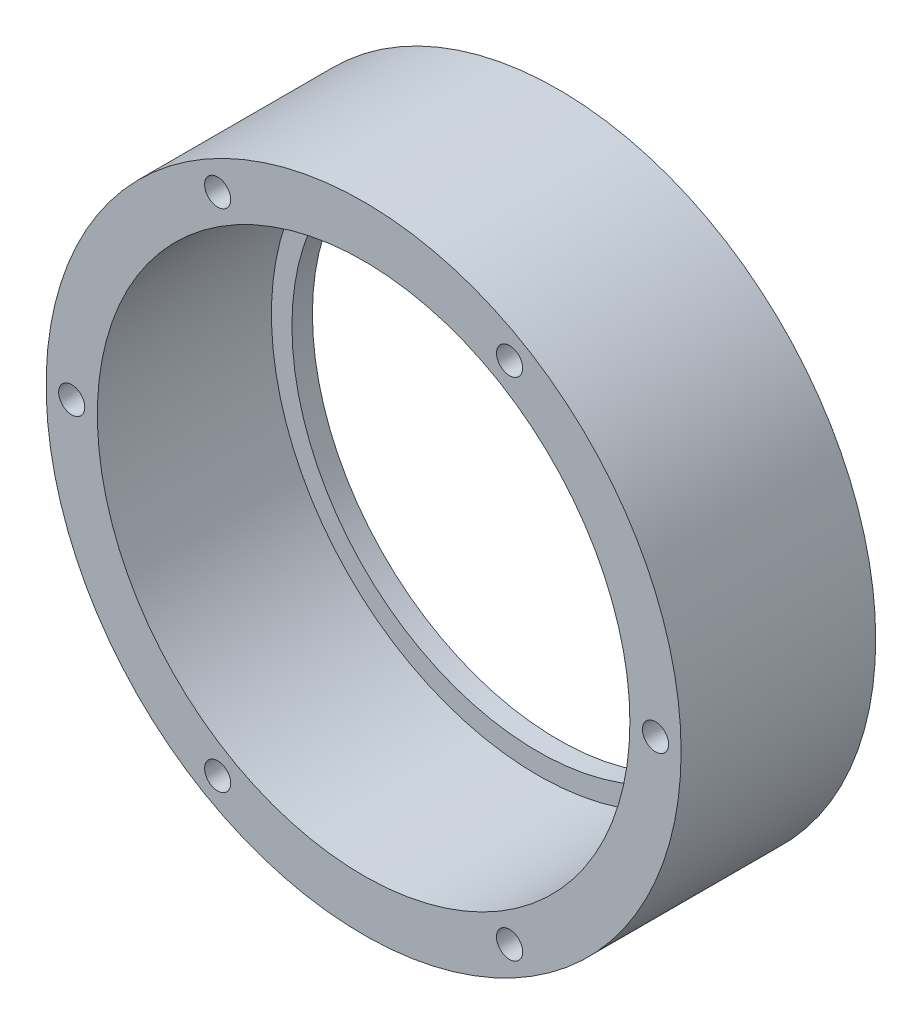
SolidWorks part; units mm, degrees
material "1060 Сплав"
ref_plane "Спереди" through (0, 0, 0) normal (0, 0, 1) x (1, 0, 0)
ref_plane "Сверху" through (0, 0, 0) normal (0, 1, 0) x (1, 0, 0)
ref_plane "Справа" through (0, 0, 0) normal (1, 0, 0) x (0, 0, -1)
sketch "Эскиз1" plane through (0, 0, 0) normal (1, 0, 0) x (0, 0, -1)
  line L3 (0, 31) -> (19, 31)
  line L4 (19, 31) -> (19, 24)
  line L6 (19, 24) -> (17, 24)
  line L7 (17, 24) -> (17, 26)
  line L8 (17, 26) -> (0, 26)
  line L9 (0, 0) -> (56.4457, 0) construction
  line L10 (0, 26) -> (0, 31)
  dimension "D1" = 52
  dimension "D2" = 48
  dimension "D3" = 62
  dimension "D4" = 2
  dimension "D5" = 19
revolve "Повернуть1" add sketch "Эскиз1" angle 360 about L9
hole_wizard "Сверло под метчик  спиральное M2.51" positions "Эскиз2" profile "Эскиз3" hole size "M2.5x0.45" standard "DIN"
sketch "Эскиз2" plane through (0, 0, 0) normal (0, 0, 1) x (1, 0, 0)
  point P0 (28.5, 0)
  dimension "D1" = 28.5
sketch "Эскиз3" plane through (28.5, 0, 0) normal (1, 0, 0) x (0, -1, 0)
  line L0 (0, 0) -> (0, 8.7661)
  line L1 (0, 8.7661) -> (1.275, 8)
  line L2 (1.275, 8) -> (1.275, 0)
  line L5 (1.275, 0) -> (0, 0)
  line L10 (0, 8.7661) -> (-1.275, 8) construction
  line L11 (0, -6.35) -> (0, 107.95) construction
  dimension "Диаметр отверстия" = 2.55
  dimension "Глубина отверстия" = 8
  dimension "Угол заточки сверла" = 118
pattern_circular "Круговой массив1" count 6 over 360 about axis through (0, 0, 0) along (0, 0, 1) of "Сверло под метчик  спиральное M2.51"
